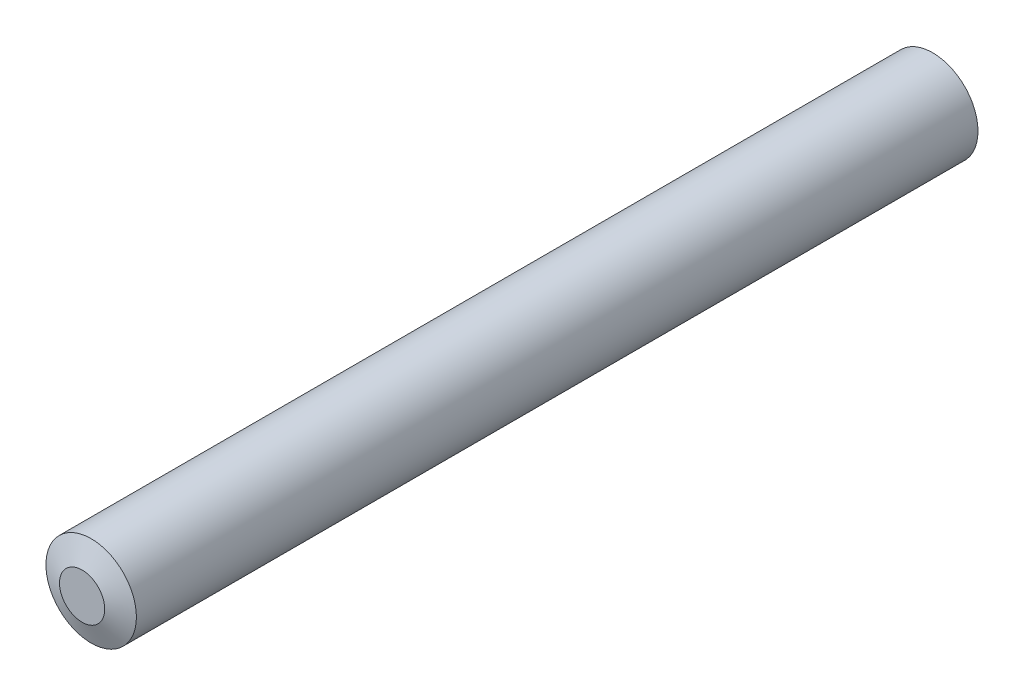
SolidWorks part; units mm, degrees
material "普通碳钢"
ref_plane "前视基准面" through (0, 0, 0) normal (0, 0, 1) x (1, 0, 0)
ref_plane "上视基准面" through (0, 0, 0) normal (0, 1, 0) x (1, 0, 0)
ref_plane "右视基准面" through (0, 0, 0) normal (1, 0, 0) x (0, 0, -1)
sketch "草图1" plane through (0, 0, 0) normal (0, 0, 1) x (1, 0, 0)
  circle A0 centre (0, 0) radius 2
  dimension "D1" = 4
extrude "拉伸1" add sketch "草图1" along normal mid plane 38
chamfer "倒角1" distance 0.4 distance2 1 1 edges at (2, 0, 19) first distance on face at (2, 0, 19)
chamfer "倒角2" distance 1 distance2 0.4 1 edges at (2, 0, -19) first distance on face at (2, 0, -19)
